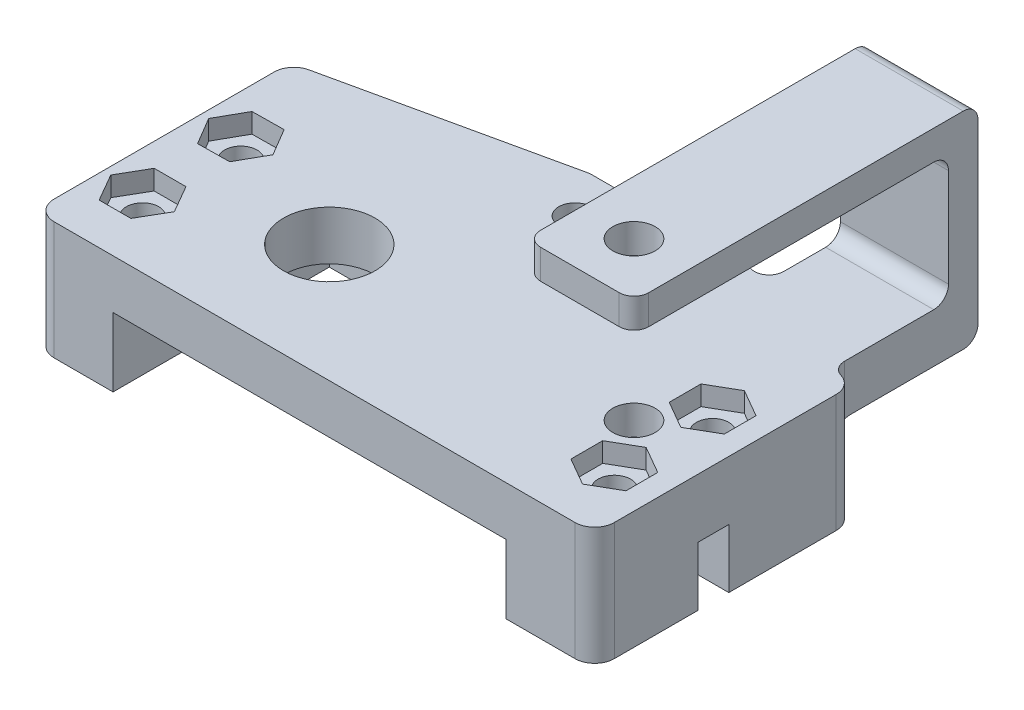
SolidWorks part; units mm, degrees
other "标注1"
sketch "草图14" plane through (64, 22, 26) normal (0.1348, 0.9386, 0.3174) x (-0.9379, 0.0175, 0.3464)
ref_plane "前视基准面" through (0, 0, 0) normal (0, 0, 1) x (1, 0, 0)
ref_plane "上视基准面" through (0, 0, 0) normal (0, 1, 0) x (1, 0, 0)
ref_plane "右视基准面" through (0, 0, 0) normal (1, 0, 0) x (0, 0, -1)
sketch "草图1" plane through (0, 0, 0) normal (0, 1, 0) x (1, 0, 0)
  line L0 (0, 0) -> (25, 5.5)
  line L2 (0, 0) -> (0, -26)
  line L3 (0, -26) -> (8, -26)
  line L4 (57, 0) -> (57, -26)
  line L7 (25, 5.5) -> (41, 5.5)
  line L10 (8, -26) -> (8, -4)
  line L11 (8, -4) -> (48, -4)
  line L12 (48, -26) -> (48, -17)
  line L13 (41, 5.5) -> (57, 0)
  line L14 (48, -26) -> (57, -26)
  line L15 (48, -11) -> (48, -4)
  circle A0 centre (4, -9) radius 1.65
  circle A1 centre (4, -19) radius 1.65
  circle A2 centre (52, -9) radius 1.65
  circle A3 centre (52, -19) radius 1.65
  circle A4 centre (28, 1) radius 1.65
  circle A5 centre (38, 1) radius 1.65
  arc A6 (48, -17) -> (48, -11) centre (49, -14) ccw
  point P12 (25, 5.5)
  point P13 (41, 5.5)
  point P14 (25, 5.5)
  point P15 (0, 0)
  dimension "D6" = 17
  dimension "D7" = 4
  dimension "D8" = 2
  dimension "D10" = 5
  dimension "D11" = 2
  dimension "D12" = 10
  dimension "D13" = 3.3
  dimension "D14" = 48
  dimension "D1" = 26
  dimension "D2" = 57
  dimension "D3" = 40
  dimension "D4" = 22
  dimension "D5" = 8
  dimension "D9" = 2
extrude "凸台-拉伸1" add sketch "草图1" along normal blind 12
sketch "草图2" plane through (0, 0, 0) normal (0, -1, 0) x (-1, 0, 0)
  line L1 (-26.6144, -1.4) -> (-25.2287, 1)
  line L2 (-25.2287, 1) -> (-26.6144, 3.4)
  line L3 (-26.6144, 3.4) -> (-29.3856, 3.4)
  line L4 (-29.3856, 3.4) -> (-30.7713, 1)
  line L5 (-30.7713, 1) -> (-29.3856, -1.4)
  line L6 (-29.3856, -1.4) -> (-26.6144, -1.4)
  line L8 (-41, 5.5) -> (-25, 5.5) construction
  line L9 (-36.6144, -1.4) -> (-35.2287, 1)
  line L10 (-35.2287, 1) -> (-36.6144, 3.4)
  line L11 (-36.6144, 3.4) -> (-39.3856, 3.4)
  line L12 (-39.3856, 3.4) -> (-40.7713, 1)
  line L13 (-40.7713, 1) -> (-39.3856, -1.4)
  line L14 (-39.3856, -1.4) -> (-36.6144, -1.4)
  circle A0 centre (-28, 1) radius 2.4 construction
  dimension "D2" = 4.8
  dimension "D1" = 2
extrude "切除-拉伸1" cut sketch "草图2" against normal blind 8
fillet "圆角1" radius 2 6 edges at (57, 6, 26) (57, 6, 0) (41, 6, -5.5) (25, 6, -5.5) (0, 6, 0) (0, 6, 26)
sketch "草图5" plane through (0, 12, 0) normal (0, 1, 0) x (1, 0, 0)
  line L0 (48, -11) -> (48, -4)
  line L1 (8, -26) -> (48, -26)
  line L2 (8, -26) -> (8, -4)
  line L3 (8, -4) -> (48, -4)
  line L4 (48, -26) -> (48, -17)
  line L5 (0, -1.6078) -> (0, -24) construction
  arc A0 (48, -17) -> (48, -11) centre (49, -14) ccw
  circle A1 centre (28, 1) radius 1.55
  circle A2 centre (38, 1) radius 1.55
  circle A3 centre (49, -14) radius 1.55
  circle A4 centre (18, -14) radius 4.6563
  dimension "D1" = 12
  dimension "D2" = 18
extrude "凸台-拉伸3" add sketch "草图5" against normal blind 5 separate body
sketch "草图6" plane through (0, 7, 0) normal (0, -1, 0) x (-1, 0, 0)
  circle A0 centre (-28, 1) radius 1.55
  circle A1 centre (-38, 1) radius 1.55
sketch "草图7" plane through (0, 7, 0) normal (0, -1, 0) x (-1, 0, 0)
  circle A0 centre (-49, -14) radius 3.15
extrude "切除-拉伸2" cut sketch "草图7" against normal blind 2
sketch "草图8" plane through (0, 0, 0) normal (0, -1, 0) x (-1, 0, 0)
  line L0 (-57, -24) -> (-57, -1.4274) construction
  line L1 (-8, -15.162) -> (0, -15.162)
  line L2 (-8, -15.162) -> (-8, -12.162)
  line L3 (-8, -12.162) -> (0, -12.162)
  line L4 (0, -15.162) -> (0, -12.162)
  line L5 (-51.7, -12.3538) -> (-57, -12.3538)
  line L6 (-51.7, -12.3538) -> (-51.7, -15.4875)
  line L7 (-51.7, -15.4875) -> (-57, -15.4875)
  line L8 (-57, -12.3538) -> (-57, -15.4875)
  line L9 (-8, -26) -> (-8, -4) construction
  arc A0 (-48, -11) -> (-48, -17) centre (-49, -14) ccw construction
  dimension "D2" = 8
  dimension "D1" = 3
extrude "切除-拉伸3" cut sketch "草图8" against normal blind 6
extrude "切除-拉伸4" cut sketch "草图6" against normal blind 10
sketch "草图17" plane through (0, 0, -5.5) normal (0, 0, -1) x (-1, 0, 0)
  line L0 (-55.6502, 12) -> (-41.316, 12) construction
  line L1 (-43.5, 12) -> (-54.5, 12)
  line L2 (-43.5, 12) -> (-43.5, 9)
  line L3 (-43.5, 9) -> (-54.5, 7)
  line L4 (-54.5, 12) -> (-54.5, 7)
  dimension "D1" = 3
extrude "凸台-拉伸9" add sketch "草图17" along normal blind 10 and the other way blind 10
sketch "草图18" plane through (0, 12, 0) normal (0, 1, 0) x (1, 0, 0)
  line L0 (54.5, 0.8594) -> (54.5, 15.5) construction
  line L1 (43.5, 15.5) -> (54.5, 15.5)
  line L2 (43.5, 15.5) -> (43.5, 12.5)
  line L3 (43.5, 12.5) -> (54.5, 12.5)
  line L4 (54.5, 15.5) -> (54.5, 12.5)
  dimension "D1" = 3
extrude "凸台-拉伸10" add sketch "草图18" along normal blind 16
sketch "草图19" plane through (0, 0, -12.5) normal (0, 0, 1) x (1, 0, 0)
  line L0 (54.5, 28) -> (54.5, 12) construction
  line L1 (43.5, 28) -> (54.5, 28)
  line L2 (43.5, 28) -> (43.5, 25)
  line L3 (43.5, 25) -> (54.5, 25)
  line L4 (54.5, 28) -> (54.5, 25)
  dimension "D1" = 3
extrude "凸台-拉伸11" add sketch "草图19" along normal blind 32
sketch "草图20" plane through (0, 28, 0) normal (0, 1, 0) x (1, 0, 0)
  circle A0 centre (49, -14) radius 2.15
  circle A1 centre (49, -14) radius 1.55 construction
extrude "切除-拉伸7" cut sketch "草图20" against normal blind 22
fillet "圆角4" radius 1.5 9 edges at (54.5, 9.5, -0.8594) (54.5, 26.5, 19.5) (43.5, 26.5, 19.5) (49, 25, -12.5) (49, 28, -15.5) (49, 12, -12.5) (49, 8, -15.5) (49, 8, -2.75) (43.5, 10.5, -4.6406)
sketch "草图21" plane through (0, 12, 0) normal (0, 1, 0) x (1, 0, 0)
  line L1 (5.5844, -6.1817) -> (2.3515, -6.2187)
  line L2 (2.3515, -6.2187) -> (0.7671, -9.037)
  line L3 (0.7671, -9.037) -> (2.4156, -11.8183)
  line L4 (2.4156, -11.8183) -> (5.6485, -11.7813)
  line L5 (5.6485, -11.7813) -> (7.2329, -8.963)
  line L6 (7.2329, -8.963) -> (5.5844, -6.1817)
  line L7 (5.6166, -16.2) -> (2.3834, -16.2)
  line L8 (2.3834, -16.2) -> (0.7668, -19)
  line L9 (0.7668, -19) -> (2.3834, -21.8)
  line L10 (2.3834, -21.8) -> (5.6166, -21.8)
  line L11 (5.6166, -21.8) -> (7.2332, -19)
  line L12 (7.2332, -19) -> (5.6166, -16.2)
  line L13 (52, -5.7668) -> (49.2, -7.3834)
  line L14 (49.2, -7.3834) -> (49.2, -10.6166)
  line L15 (49.2, -10.6166) -> (52, -12.2332)
  line L16 (52, -12.2332) -> (54.8, -10.6166)
  line L17 (54.8, -10.6166) -> (54.8, -7.3834)
  line L18 (54.8, -7.3834) -> (52, -5.7668)
  line L19 (52, -15.7668) -> (49.2, -17.3834)
  line L20 (49.2, -17.3834) -> (49.2, -20.6166)
  line L21 (49.2, -20.6166) -> (52, -22.2332)
  line L22 (52, -22.2332) -> (54.8, -20.6166)
  line L23 (54.8, -20.6166) -> (54.8, -17.3834)
  line L24 (54.8, -17.3834) -> (52, -15.7668)
  line L25 (57, -24) -> (57, -1.4274) construction
  circle A0 centre (4, -9) radius 2.8 construction
  circle A1 centre (4, -19) radius 2.8 construction
  circle A2 centre (52, -9) radius 2.8 construction
  circle A3 centre (52, -19) radius 2.8 construction
  point P40 (-16.1037, 4.4274)
  dimension "D1" = 5.6
  dimension "D2" = 5.6
  dimension "D3" = 5.6
  dimension "D4" = 5.6
extrude "切除-拉伸8" cut sketch "草图21" against normal blind 2
